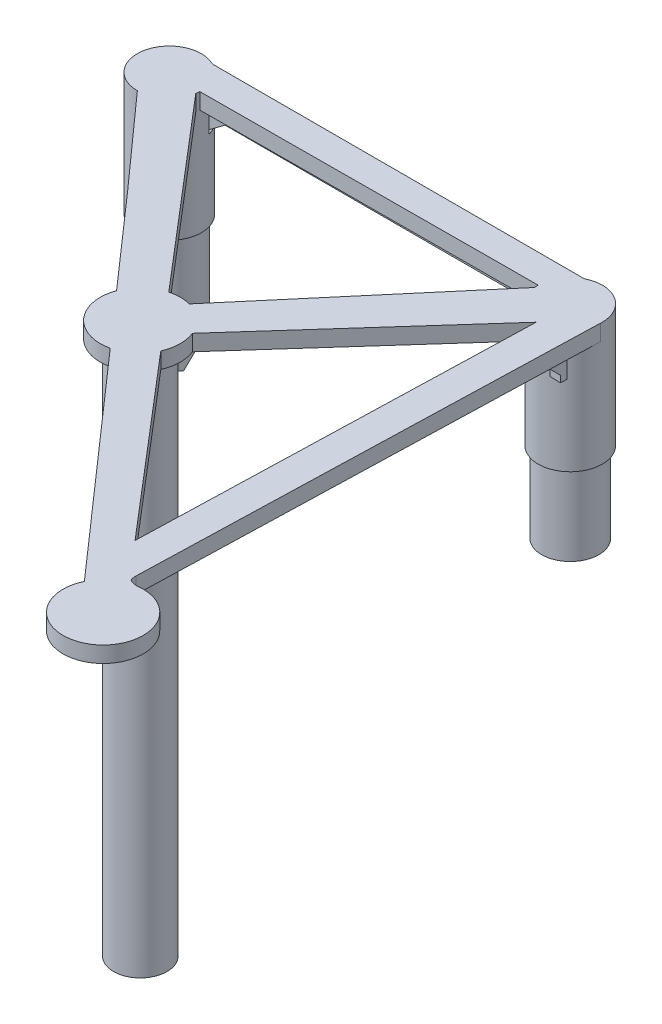
SolidWorks part; units mm, degrees
ref_plane "前视基准面" through (0, 0, 0) normal (0, 0, 1) x (1, 0, 0)
ref_plane "上视基准面" through (0, 0, 0) normal (0, 1, 0) x (1, 0, 0)
ref_plane "右视基准面" through (0, 0, 0) normal (1, 0, 0) x (0, 0, -1)
sketch "草图1" plane through (0, 0, 0) normal (0, 1, 0) x (1, 0, 0)
  line L1 (-18.6554, 0) -> (18.8446, -42.931)
  line L2 (18.8446, -42.931) -> (56.3446, 0)
  line L3 (-18.6554, 0) -> (56.3446, 0)
  dimension "D4" = 75
extrude "凸台-拉伸1" add sketch "草图1" along normal blind 3
sketch "草图2" plane through (0, 3, 0) normal (0, 1, 0) x (1, 0, 0)
  circle A0 centre (56.3446, 0) radius 5.35
  circle A1 centre (-18.6554, 0) radius 5.35
  dimension "D1" = 10.7
  dimension "D2" = 10.7
extrude "凸台-拉伸2" add sketch "草图2" against normal blind 23
sketch "草图3" plane through (0, 0, 0) normal (0, -1, 0) x (1, 0, 0)
  line L6 (8.6327, 17.5594) -> (1.1561, 9)
  line L7 (1.1561, 9) -> (33.7591, 9)
  line L8 (8.6327, 17.5594) -> (18.8446, 29.2503)
  line L9 (18.8446, 29.2503) -> (29.0566, 17.5594)
  line L10 (29.0566, 17.5594) -> (36.5332, 9)
  line L11 (36.5332, 9) -> (33.7591, 9)
  dimension "D4" = 26.8879
  dimension "D5" = 26.8879
  dimension "D6" = 35.3771
extrude "切除-拉伸1" cut sketch "草图3" against normal blind 3
sketch "草图4" plane through (0, 0, 0) normal (0, -1, 0) x (1, 0, 0)
  circle A0 centre (18.8446, 42.931) radius 5
  dimension "D1" = 10
extrude "凸台-拉伸3" add sketch "草图4" along normal blind 100
sketch "草图5" plane through (0, 0, 0) normal (0, 1, 0) x (1, 0, 0)
  circle A0 centre (18.8446, -42.931) radius 5
extrude "凸台-拉伸4" add sketch "草图5" along normal blind 3
sketch "草图6" plane through (0, -20, 0) normal (0, -1, 0) x (1, 0, 0)
  circle A0 centre (56.3446, 0) radius 5.35
extrude "凸台-拉伸5" add sketch "草图6" along normal blind 5
sketch "草图7" plane through (0, -20, 0) normal (0, -1, 0) x (1, 0, 0)
  circle A0 centre (-18.6554, 0) radius 5.35
extrude "凸台-拉伸6" add sketch "草图7" along normal blind 5
sketch "草图8" plane through (0, 3, 0) normal (0, 1, 0) x (1, 0, 0)
  line L0 (-18.6554, 5.35) -> (56.3446, 5.35)
  line L1 (56.3446, 5.35) -> (56.3446, -5.35)
  line L2 (56.3446, -5.35) -> (-18.6554, -5.35)
  line L3 (-18.6554, -5.35) -> (-18.6554, 5.35)
  arc A1 (52.8251, -4.0293) -> (50.9946, 0) centre (56.3446, 0) ccw construction
  arc A2 (-13.3054, 0) -> (-15.1358, -4.0293) centre (-18.6554, 0) ccw construction
  circle A3 centre (-18.6554, 0) radius 5.35 construction
extrude "凸台-拉伸7" add sketch "草图8" against normal blind 3
sketch "草图9" plane through (0, 3, 0) normal (0, 1, 0) x (1, 0, 0)
  line L0 (61.6946, 0) -> (18.8446, -47.931)
  line L1 (18.8446, -47.931) -> (-24.0054, 0)
  line L2 (-24.0054, 0) -> (61.6946, 0)
  arc A0 (56.3446, -5.35) -> (56.3446, 5.35) centre (56.3446, 0) ccw construction
  arc A1 (15.5553, -39.1653) -> (22.134, -39.1653) centre (18.8446, -42.931) ccw construction
  arc A2 (-18.6554, 5.35) -> (-18.6554, -5.35) centre (-18.6554, 0) ccw construction
extrude "凸台-拉伸8" add sketch "草图9" against normal blind 3
sketch "草图10" plane through (0, 0, 0) normal (0, -1, 0) x (1, 0, 0)
  line L0 (18.8446, 37.931) -> (-13.3137, 0.299)
  line L1 (-13.3137, 0.299) -> (50.9946, 0)
  line L2 (50.9946, 0) -> (18.8446, 37.931)
  arc A0 (13.8759, 42.373) -> (23.8134, 42.373) centre (18.8446, 42.931) ccw construction
  arc A1 (-18.6554, -5.35) -> (-19.2524, 5.3166) centre (-18.6554, 0) ccw construction
  circle A2 centre (56.3446, 0) radius 5.35 construction
  arc A3 (56.9416, 5.3166) -> (56.3446, -5.35) centre (56.3446, 0) ccw construction
extrude "切除-拉伸2" cut sketch "草图10" against normal blind 3
sketch "草图12" plane through (0, 3, 0) normal (0, 1, 0) x (1, 0, 0)
  circle A0 centre (-18.6554, 0) radius 6
  circle A1 centre (56.3446, 0) radius 6
  dimension "D1" = 12
  dimension "D2" = 12
extrude "凸台-拉伸10" add sketch "草图12" against normal blind 13
sketch "草图13" plane through (0, -25, 0) normal (0, -1, 0) x (1, 0, 0)
  circle A0 centre (-18.6554, 0) radius 3
  circle A1 centre (56.3446, 0) radius 3
  dimension "D1" = 6
  dimension "D2" = 6
extrude "切除-拉伸3" cut sketch "草图13" against normal blind 23
sketch "草图14" plane through (0, -100, 0) normal (0, -1, 0) x (1, 0, 0)
  circle A0 centre (18.8446, 42.931) radius 3.125
  dimension "D1" = 6.25
extrude "切除-拉伸5" cut sketch "草图14" against normal blind 100
sketch "草图15" plane through (0, -10, 0) normal (0, -1, 0) x (1, 0, 0)
  circle A0 centre (56.3446, 0) radius 5.35
  circle A1 centre (56.3446, 0) radius 6
extrude "凸台-拉伸11" add sketch "草图15" along normal blind 5
sketch "草图16" plane through (0, -10, 0) normal (0, -1, 0) x (1, 0, 0)
  circle A0 centre (-18.6554, 0) radius 3
  circle A1 centre (-18.6554, 0) radius 6
extrude "凸台-拉伸12" add sketch "草图16" along normal blind 5
sketch "草图17" plane through (0, -25, 0) normal (0, -1, 0) x (1, 0, 0)
  circle A0 centre (-18.6554, 0) radius 3
  circle A1 centre (-18.6554, 0) radius 5.35
extrude "凸台-拉伸13" add sketch "草图17" along normal blind 5
sketch "草图18" plane through (0, -25, 0) normal (0, -1, 0) x (1, 0, 0)
  circle A0 centre (56.3446, 0) radius 3
  circle A1 centre (56.3446, 0) radius 5.35
extrude "凸台-拉伸14" add sketch "草图18" along normal blind 5
sketch "草图20" plane through (0, -15, 0) normal (0, -1, 0) x (1, 0, 0)
  circle A0 centre (-18.6554, 0) radius 5.35
  circle A1 centre (-18.6554, 0) radius 6
extrude "凸台-拉伸15" add sketch "草图20" along normal blind 5
sketch "草图21" plane through (0, -15, 0) normal (0, -1, 0) x (1, 0, 0)
  circle A0 centre (56.3446, 0) radius 5.35
  circle A1 centre (56.3446, 0) radius 6
extrude "凸台-拉伸16" add sketch "草图21" along normal blind 5
sketch "草图22" plane through (0, -30, 0) normal (0, -1, 0) x (1, 0, 0)
  circle A0 centre (-18.6554, 0) radius 3
  circle A1 centre (-18.6554, 0) radius 5.35
extrude "凸台-拉伸17" add sketch "草图22" along normal blind 5
sketch "草图23" plane through (0, -30, 0) normal (0, -1, 0) x (1, 0, 0)
  circle A0 centre (56.3446, 0) radius 3
  circle A1 centre (56.3446, 0) radius 5.35
extrude "凸台-拉伸18" add sketch "草图23" along normal blind 5
sketch "草图25" plane through (0, 3, 0) normal (0, 1, 0) x (1, 0, 0)
  circle A0 centre (18.8446, -42.931) radius 7.5
  dimension "D1" = 15
extrude "凸台-拉伸20" add sketch "草图25" against normal blind 3
sketch "草图28" plane through (0, 3, 0) normal (0, 1, 0) x (1, 0, 0)
  line L1 (-3.3796, -23.0714) -> (2.0936, -18.3287)
  line L2 (-3.3796, -23.0714) -> (64.3216, -100.0268)
  line L3 (64.3216, -100.0268) -> (66.8686, -97.9101)
  line L4 (-18.6414, -6) -> (11.8821, -40.1429) construction
  line L5 (2.0936, -18.3287) -> (68.6526, -96.2167)
  line L6 (16.9224, -35.6815) -> (-12.7353, -0.9759) construction
  line L7 (68.6526, -96.2167) -> (66.8686, -97.9101)
extrude "凸台-拉伸21" add sketch "草图28" against normal blind 3
sketch "草图29" plane through (0, 3, 0) normal (0, 1, 0) x (1, 0, 0)
  line L0 (56.3446, 0) -> (53.7411, -88)
  line L1 (20.5226, -50.2409) -> (64.3216, -100.0268) construction
  line L2 (53.7411, -88) -> (59.7411, -88)
  line L3 (56.3446, 0) -> (62.3446, 0)
  line L4 (62.3446, 0) -> (59.7411, -88)
  arc A1 (56.3307, -6) -> (53.6285, 5.35) centre (56.3446, 0) ccw construction
  dimension "D2" = 6
  dimension "D3" = 88
extrude "凸台-拉伸23" add sketch "草图29" against normal blind 3
sketch "草图30" plane through (0, 3, 0) normal (0, 1, 0) x (1, 0, 0)
  circle A0 centre (62.6532, -93.6946) radius 7.5
  dimension "D1" = 15
extrude "凸台-拉伸24" add sketch "草图30" against normal blind 3
fillet "圆角1" radius 3 2 edges at (60.3876, 1.5, 86.545) (59.8043, 1.5, 85.8624)
sketch "草图31" plane through (0, 0, 0) normal (0, -1, 0) x (1, 0, 0)
  line L0 (-14.7236, -1.6282) -> (-14.7236, -3.6282)
  line L1 (-14.7236, -3.6282) -> (53.5274, -3.6282)
  line L2 (53.5274, -3.6282) -> (53.8249, -1.6282)
  line L3 (53.8249, -1.6282) -> (-14.7236, -1.6282)
  line L4 (49.6098, 80.1025) -> (51.1303, 78.8032)
  line L5 (22.3188, 45.0877) -> (51.1303, 78.8032)
  line L6 (49.6098, 80.1025) -> (20.7983, 46.387)
  line L7 (-15.3496, 4.0864) -> (-13.8291, 2.7871)
  line L8 (20.3259, 39.1868) -> (51.8689, 1.9719)
  line L9 (20.3259, 39.1868) -> (21.8516, 40.4799)
  line L10 (51.8689, 1.9719) -> (53.3946, 3.265)
  line L11 (21.8516, 40.4799) -> (53.3946, 3.265)
  line L12 (20.7983, 46.387) -> (22.3188, 45.0877)
  line L13 (15.5768, 40.2768) -> (17.0973, 38.9775)
  line L14 (17.0973, 38.9775) -> (-13.8291, 2.7871)
  line L15 (-15.3496, 4.0864) -> (15.5768, 40.2768)
  line L16 (56.0939, 78.8643) -> (58.3189, 3.6596)
  line L17 (58.3189, 3.6596) -> (60.3198, 3.6596)
  line L18 (60.3198, 3.6596) -> (58.093, 78.9234)
  line L19 (58.093, 78.9234) -> (56.0939, 78.8643)
  circle A0 centre (-18.6554, 0) radius 5.35 construction
  circle A1 centre (56.3446, 0) radius 3 construction
  dimension "D1" = 2
  dimension "D2" = 2
  dimension "D3" = 2
  dimension "D4" = 2
  dimension "D5" = 2
extrude "凸台-拉伸29" add sketch "草图31" along normal blind 5
sketch "草图35" plane through (0, 0, -3.6282) normal (0, 0, -1) x (-1, 0, 0)
  line L0 (13.8766, -5) -> (9.8766, -2)
  line L1 (9.8766, -2) -> (-47.5659, -2)
  line L2 (-47.5659, -2) -> (-51.5659, -5)
  line L3 (-51.5659, -5) -> (13.8766, -5)
  line L4 (13.8766, 0) -> (-51.5659, 0) construction
  dimension "D1" = 2
  dimension "D2" = 4
  dimension "D3" = 4
sketch "草图36" plane through (0, -5, 0) normal (0, -1, 0) x (1, 0, 0)
  line L0 (18.8446, -3.6282) -> (18.8446, -1.6282)
  line L1 (-9.8766, -3.6282) -> (47.5659, -3.6282) construction
  line L2 (50.5698, -1.6282) -> (-12.8805, -1.6282) construction
sweep "切除-扫描1" cut profiles "草图35" path "草图36"
sketch "草图37" plane through (60.3752, 0, 1.7863) normal (0.9996, 0, 0.0296) x (0.0296, 0, -0.9996)
  line L0 (-2.7315, -5) -> (-6.7315, -1)
  line L1 (-6.7315, -1) -> (-73.1709, -1)
  line L2 (-73.1709, -1) -> (-77.1709, -5)
  line L3 (-77.1709, -5) -> (-2.7315, -5)
  line L5 (-82.8983, 0) -> (1.4889, 0) construction
  dimension "D1" = 1
  dimension "D2" = 4
  dimension "D3" = 4
sketch "草图38" plane through (0, -5, 0) normal (0, -1, 0) x (1, 0, 0)
  line L0 (59.1937, 41.72) -> (57.1928, 41.72)
  line L1 (60.1761, 8.5148) -> (58.2113, 74.9252) construction
  line L2 (56.0939, 78.8643) -> (58.2589, 5.6864) construction
sweep "切除-扫描3" cut profiles "草图37" path "草图38"
sketch "草图39" plane through (58.3761, 0, 1.7271) normal (0.9996, 0, 0.0296) x (0.0296, 0, -0.9996)
  line L0 (-3.961, -3.8296) -> (-3.961, -5)
  line L1 (-3.961, -5) -> (-2.7315, -5)
  line L2 (-3.961, -3.8296) -> (-3.961, -3.2722)
  line L3 (-3.961, -3.2722) -> (-2.7315, -4.5017)
  line L4 (-2.7315, 0) -> (-2.7315, -5) construction
  line L5 (-2.7315, -4.5017) -> (-2.7315, -5)
extrude "凸台-拉伸31" add sketch "草图39" along normal blind 2
sketch "草图40" plane through (-10.8895, 0, 9.3056) normal (-0.7602, 0, 0.6497) x (0.6497, 0, 0.7602)
  line L0 (-5.1212, -5) -> (-3.1212, -1)
  line L2 (39.938, -5) -> (-6.1212, -5) construction
  line L3 (-3.1212, -1) -> (36.938, -1)
  line L5 (36.938, -1) -> (38.938, -5)
  line L6 (38.938, -5) -> (-5.1212, -5)
  line L7 (39.938, 0) -> (-6.1212, 0) construction
  dimension "D1" = 1
  dimension "D2" = 2
  dimension "D3" = 1
  dimension "D4" = 1
  dimension "D5" = 2
sketch "草图42" plane through (0, -5, 0) normal (0, -1, 0) x (1, 0, 0)
  line L0 (0.0951, 22.1599) -> (1.5521, 20.7864)
  line L1 (-12.9172, 6.9328) -> (13.1074, 37.387) construction
  line L2 (-13.5363, 3.1298) -> (16.6406, 38.443) construction
sweep "切除-扫描5" cut profiles "草图40" path "草图42"
sketch "草图43" plane through (31.1568, 0, 26.4083) normal (-0.7628, 0, -0.6466) x (-0.6466, 0, 0.7628)
  line L0 (14.7346, -5) -> (12.7346, -1)
  line L1 (15.7346, -5) -> (-30.8257, -5) construction
  line L2 (12.7346, -1) -> (-27.8257, -1)
  line L3 (-27.8257, -1) -> (-29.8257, -5)
  line L4 (14.7346, -5) -> (-29.8257, -5)
  line L5 (15.7346, 0) -> (-30.8257, 0) construction
  dimension "D1" = 1
  dimension "D2" = 1
  dimension "D3" = 1
  dimension "D4" = 2
  dimension "D5" = 2
sketch "草图44" plane through (0, -5, 0) normal (0, -1, 0) x (1, 0, 0)
  line L0 (36.0357, 20.6522) -> (37.4729, 22.0498)
  line L1 (22.9229, 36.1228) -> (49.1484, 5.1816) construction
  line L2 (52.36, 4.4858) -> (22.5858, 39.6138) construction
sweep "切除-扫描6" cut profiles "草图43" path "草图44"
sketch "草图46" plane through (-10.8895, 0, 9.3056) normal (-0.7602, 0, 0.6497) x (0.6497, 0, 0.7602)
  line L0 (50.8218, -5) -> (52.8218, -1)
  line L1 (93.1256, -5) -> (49.8218, -5) construction
  line L2 (52.8218, -1) -> (88.1256, -1)
  line L3 (88.1256, -1) -> (93.1256, 0)
  line L4 (93.1256, 0) -> (93.1256, -5)
  line L5 (93.1256, -5) -> (50.8218, -5)
  line L6 (93.1256, 0) -> (49.8218, 0) construction
  dimension "D1" = 1
  dimension "D2" = 1
  dimension "D3" = 2
  dimension "D4" = 5
sketch "草图47" plane through (0, -5, 0) normal (0, -1, 0) x (1, 0, 0)
  line L0 (37.0322, 62.3055) -> (35.5118, 63.6048)
  line L1 (22.9341, 45.8078) -> (51.1303, 78.8032) construction
  line L2 (23.4264, 49.4624) -> (46.3616, 76.3014) construction
sweep "切除-扫描7" cut profiles "草图46" path "草图47"
sketch "草图48" plane through (60.3752, 0, 1.7863) normal (0.9996, 0, 0.0296) x (0.0296, 0, -0.9996)
  line L0 (-73.1709, -1) -> (-77.1709, 0)
  line L1 (-77.1709, 0) -> (-77.1709, -5)
  line L2 (-73.1709, -1) -> (-77.1709, -5)
sketch "草图49" plane through (0, -1, 0) normal (0, -1, 0) x (1, 0, 0)
  line L0 (58.2113, 74.9252) -> (56.2104, 74.9252)
  line L1 (56.2104, 74.9252) -> (55.38, 74.9252)
sweep "切除-扫描8" cut profiles "草图48" path "草图49"
